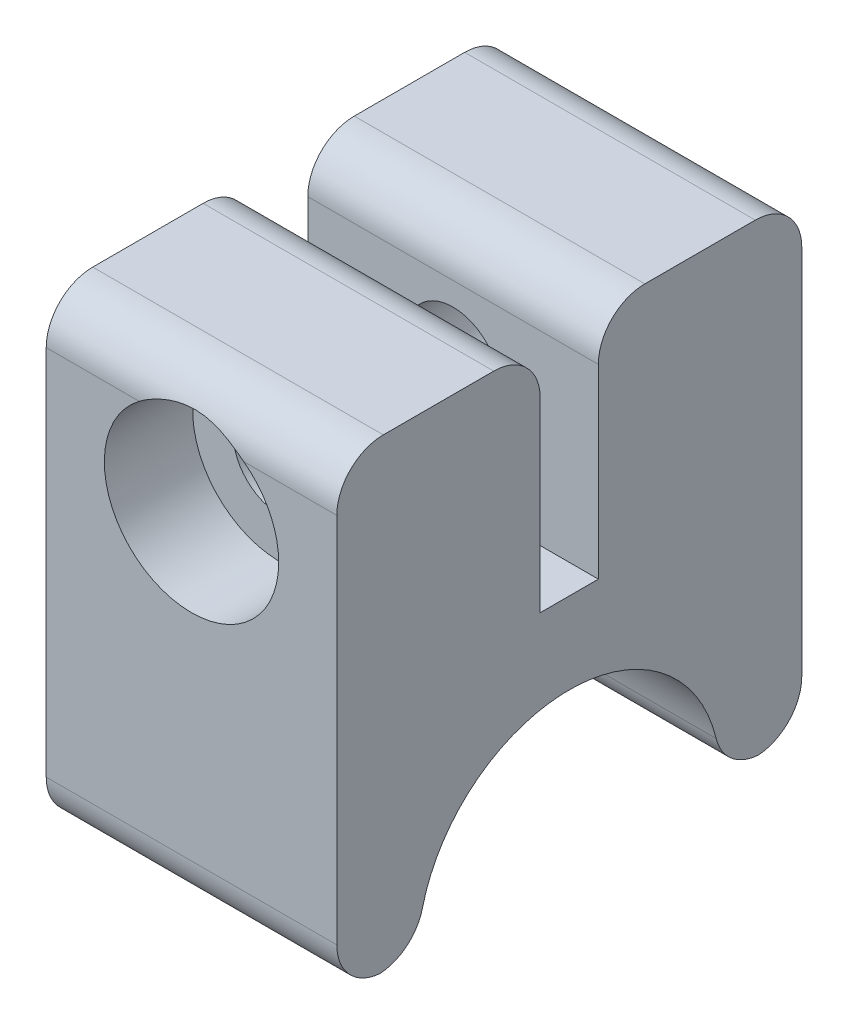
SolidWorks part; units mm, degrees
material "Delrin 2700 NC010, Low Viscosity Acetal Copolymer (SS)"
ref_plane "Front Plane" through (0, 0, 0) normal (0, 0, 1) x (1, 0, 0)
ref_plane "Top Plane" through (0, 0, 0) normal (0, 1, 0) x (1, 0, 0)
ref_plane "Right Plane" through (0, 0, 0) normal (1, 0, 0) x (0, 0, -1)
sketch "Sketch1" plane through (0, 0, 0) normal (0, 0, 1) x (1, 0, 0)
  line L1 (-7.9375, -12.7) -> (7.9375, -12.7)
  line L2 (-7.9375, -12.7) -> (-7.9375, 12.7)
  line L3 (-7.9375, 12.7) -> (7.9375, 12.7)
  line L4 (7.9375, -12.7) -> (7.9375, 12.7)
  line L5 (-7.9375, -12.7) -> (7.9375, 12.7) construction
  line L6 (-7.9375, 12.7) -> (7.9375, -12.7) construction
  point P0 (0, 0)
  dimension "D1" = 15.875
  dimension "D2" = 25.4
extrude "Boss-Extrude1" add sketch "Sketch1" along normal mid plane 25.4
sketch "Sketch2" plane through (7.9375, 0, 0) normal (1, 0, 0) x (0, 0, -1)
  line L0 (-12.7, 12.7) -> (12.7, 12.7) construction
  line L1 (-1.5875, 12.7) -> (1.5875, 12.7)
  line L2 (-1.5875, 12.7) -> (-1.5875, 0)
  line L3 (-1.5875, 0) -> (1.5875, 0)
  line L4 (1.5875, 12.7) -> (1.5875, 0)
  line L5 (-12.7, 12.7) -> (-1.5875, 12.7) construction
  line L6 (1.5875, 12.7) -> (12.7, 12.7) construction
  line L7 (-12.7, -12.7) -> (12.7, -12.7) construction
  circle A0 centre (0, -12.7) radius 8.255
  dimension "D3" = 16.51
  dimension "D1" = 3.175
  dimension "D2" = 12.7
extrude "Cut-Extrude1" cut sketch "Sketch2" against normal through all
hole_wizard "CBORE for #10 Socket Head Cap Screw1" positions "Sketch3" profile "Sketch4" counterbore size "#10" standard "ANSI Inch" end condition through all
sketch "Sketch3" plane through (0, 0, 12.7) normal (0, 0, 1) x (1, 0, 0)
  line L0 (7.9375, 12.7) -> (-7.9375, 12.7) construction
  point P0 (0, 6.35)
  dimension "D1" = 6.35
sketch "Sketch4" plane through (0, 6.35, 12.7) normal (1, 0, 0) x (0, -1, 0)
  line L0 (0, 0) -> (0, 25.4)
  line L1 (0, 25.4) -> (2.5527, 25.4)
  line L3 (2.5527, 25.4) -> (2.5527, 4.826)
  line L4 (2.5527, 4.826) -> (4.7625, 4.826)
  line L5 (4.7625, 4.826) -> (4.7625, 0)
  line L7 (4.7625, 0) -> (0, 0)
  line L11 (0, -6.35) -> (0, 107.95) construction
  dimension "Thru Hole Dia." = 5.1054
  dimension "Thru Hole Depth" = 25.4
  dimension "C'Bore Dia." = 9.525
  dimension "C'Bore Depth" = 4.826
fillet "Fillet2" radius 2.54 8 edges at (0, -12.7, 8.255) (0, -12.7, -8.255) (0, 12.7, 12.7) (0, -12.7, 12.7) (0, 12.7, -12.7) (0, 12.7, -1.5875) (0, 12.7, 1.5875) (0, -12.7, -12.7)
sketch "Sketch5" plane through (0, 0, -12.7) normal (0, 0, -1) x (-1, 0, 0)
  line L1 (5.6459, 6.35) -> (2.823, 11.2395)
  line L2 (2.823, 11.2395) -> (-2.823, 11.2395)
  line L3 (-2.823, 11.2395) -> (-5.6459, 6.35)
  line L4 (-5.6459, 6.35) -> (-2.823, 1.4605)
  line L5 (-2.823, 1.4605) -> (2.823, 1.4605)
  line L6 (2.823, 1.4605) -> (5.6459, 6.35)
  circle A0 centre (0, 6.35) radius 4.8895 construction
  dimension "D1" = 9.779
extrude "Cut-Extrude2" cut sketch "Sketch5" against normal blind 6.2071
